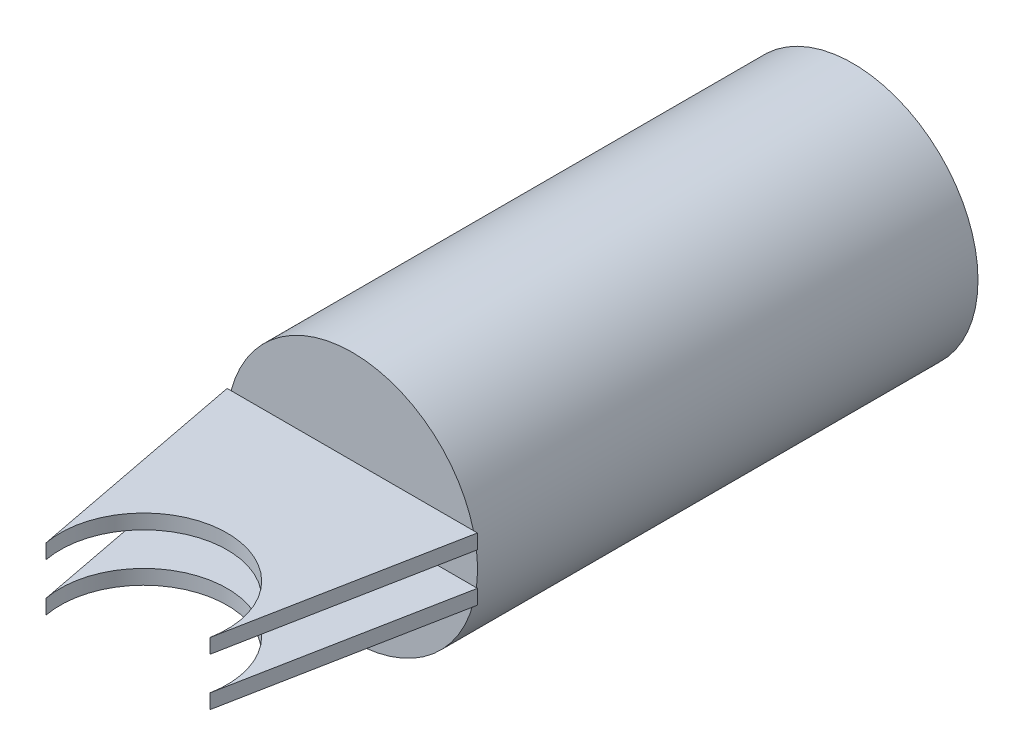
SolidWorks part; units mm, degrees
ref_plane "Front Plane" through (0, 0, 0) normal (0, 0, 1) x (1, 0, 0)
ref_plane "Top Plane" through (0, 0, 0) normal (0, 1, 0) x (1, 0, 0)
ref_plane "Right Plane" through (0, 0, 0) normal (1, 0, 0) x (0, 0, -1)
sketch "Pole Sketch" plane through (0, 0, 0) normal (0, 0, 1) x (1, 0, 0)
  circle A0 centre (0, 0) radius 30
  dimension "D1" = 60
extrude "Pole Extrude" add sketch "Pole Sketch" against normal blind 120
sketch "Palm Holder Sketch" plane through (0, 0, 0) normal (0, 1, 0) x (1, 0, 0)
  line L0 (19.6389, -53.7833) -> (30, 0)
  line L1 (30, 0) -> (-30, 0)
  line L2 (-30, 0) -> (-19.6389, -53.7833)
  line L4 (19.6389, -53.7833) -> (-19.6389, -53.7833) construction
  arc A0 (19.6389, -53.7833) -> (-19.6389, -53.7833) centre (0, -50) ccw
  dimension "D1" = 40
  dimension "D2" = 50
extrude "Upper Palm Holder Extrude" add sketch "Palm Holder Sketch" along normal blind 3.5 from offset 4
extrude "Lower Palm Holder Extrude" add sketch "Palm Holder Sketch<2>" against normal blind 3.5 from offset 4 offset against normal yes
sketch "Palm Holder Sketch<2>" plane through (0, 0, 0) normal (0, 1, 0) x (1, 0, 0) same geometry as "Palm Holder Sketch"
